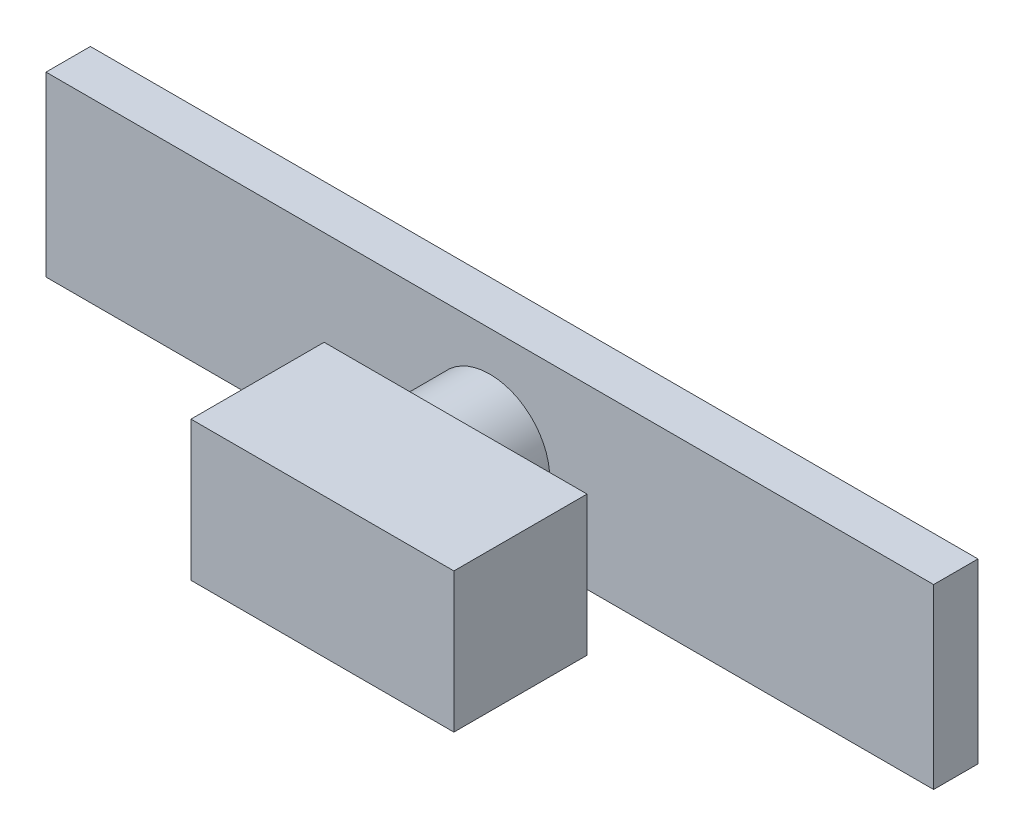
SolidWorks part; units mm, degrees
ref_plane "Front Plane" through (0, 0, 0) normal (0, 0, 1) x (1, 0, 0)
ref_plane "Top Plane" through (0, 0, 0) normal (0, 1, 0) x (1, 0, 0)
ref_plane "Right Plane" through (0, 0, 0) normal (1, 0, 0) x (0, 0, -1)
sketch "Sketch2" plane through (0, 0, 0) normal (0, 0, 1) x (1, 0, 0)
  line L1 (-47.8692, 21.2481) -> (206.1308, 21.2481)
  line L2 (-47.8692, 21.2481) -> (-47.8692, 8.5481)
  line L3 (-47.8692, 8.5481) -> (206.1308, 8.5481)
  line L4 (206.1308, 21.2481) -> (206.1308, 8.5481)
  dimension "D1" = 12.7
  dimension "D2" = 254
extrude "Boss-Extrude1" add sketch "Sketch2" along normal blind 50.8
sketch "Sketch3" plane through (0, 21.2481, 0) normal (0, 1, 0) x (1, 0, 0)
  circle A0 centre (79.1308, -28.4831) radius 17.1408
extrude "Boss-Extrude2" add sketch "Sketch3" along normal blind 19.05
sketch "Sketch4" plane through (0, 40.2981, 0) normal (0, 1, 0) x (1, 0, 0)
  line L1 (50.7675, -8.111) -> (126.0034, -8.111)
  line L2 (50.7675, -8.111) -> (50.7675, -48.0661)
  line L3 (50.7675, -48.0661) -> (126.0034, -48.0661)
  line L4 (126.0034, -8.111) -> (126.0034, -48.0661)
extrude "Boss-Extrude3" add sketch "Sketch4" along normal blind 38.1
scale "Scale2" scale about centroid uniform scaling yes scale factor 0.06
move or copy body "Body-Move/Copy1" bodies to move or copy 105 copy no rotation origin (0, 33.6669, 26.5501) rotation axis (1, 0, 0) rotation angle 90
move or copy body "Body-Move/Copy3" bodies to move or copy 106 copy no translate (-50.8, 0, -50.8)
scale "Scale5" scale about centroid uniform scaling yes scale factor 0.25
move or copy body "Body-Move/Copy9" bodies to move or copy 111 copy no translate (-50.8, 0, 0)
